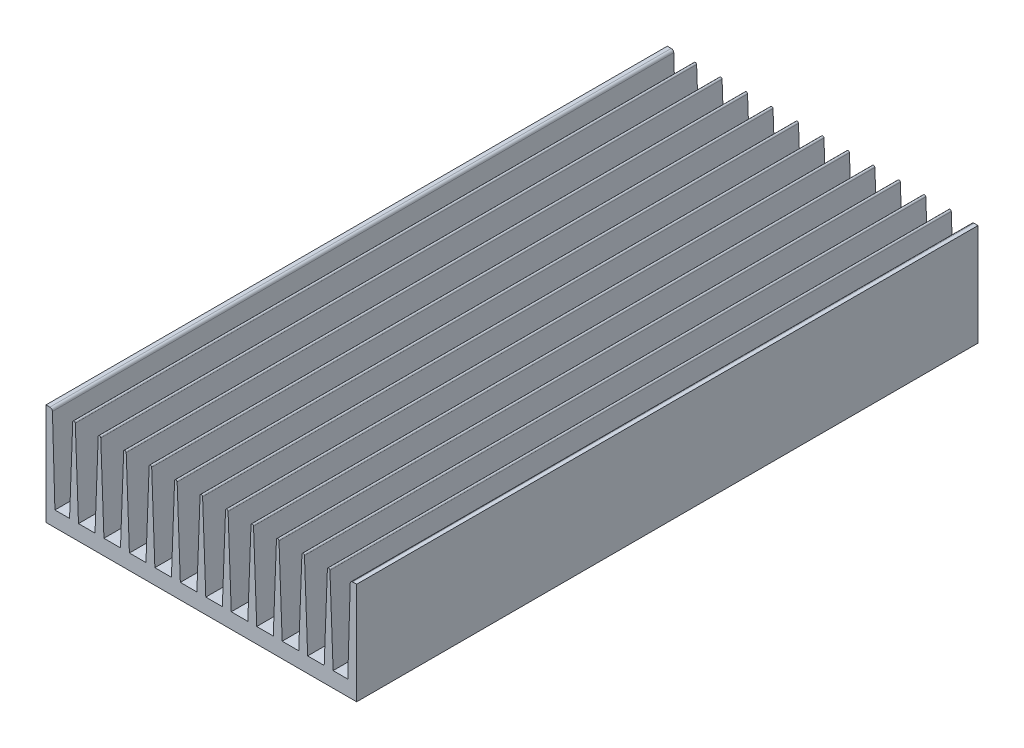
SolidWorks part; units mm, degrees
ref_plane "Спереди" through (0, 0, 0) normal (0, 0, 1) x (1, 0, 0)
ref_plane "Сверху" through (0, 0, 0) normal (0, 1, 0) x (1, 0, 0)
ref_plane "Справа" through (0, 0, 0) normal (1, 0, 0) x (0, 0, -1)
sketch "Эскиз1" plane through (0, 0, 0) normal (0, 0, 1) x (1, 0, 0)
  line L0 (0, 40) -> (1.529, 40)
  line L1 (0, 0) -> (122, 0)
  line L2 (2.5285, 39.0294) -> (3.5, 6)
  line L3 (0, 40) -> (0, 0)
  line L4 (122, 40) -> (122, 0)
  line L5 (61, 63.7127) -> (61, -22.2582) construction
  line L8 (122, 40) -> (120.471, 40)
  line L9 (119.4715, 39.0294) -> (118.5, 6)
  line L10 (3.5, 6) -> (118.5, 6)
  arc A0 (1.529, 40) -> (2.5285, 39.0294) centre (1.529, 39) cw
  arc A2 (120.471, 40) -> (119.4715, 39.0294) centre (120.471, 39) ccw
  point P18 (119.5, 40)
  dimension "D9" = 1
  dimension "D1" = 122
  dimension "D2" = 6
  dimension "D3" = 40
  dimension "D4" = 3.5
  dimension "D7" = 2.5
extrude "Вытянуть1" add sketch "Эскиз1" along normal blind 244
sketch "Эскиз2" plane through (0, 0, 244) normal (0, 0, 1) x (1, 0, 0)
  line L0 (118.5, 6) -> (3.5, 6) construction
  line L1 (10.5, 39.5) -> (9.25, 6)
  line L2 (11, 39.5) -> (11, 22.5548) construction
  line L3 (11.5, 39.5) -> (12.75, 6)
  line L4 (9.25, 6) -> (12.75, 6)
  line L6 (0, 40) -> (0, 0) construction
  arc A0 (10.5, 39.5) -> (11.5, 39.5) centre (11, 39.5) cw
  dimension "D1" = 34
  dimension "D3" = 0.5
  dimension "D2" = 3.5
  dimension "D4" = 11
  dimension "D5" = 1
extrude "Вытянуть3" add sketch "Эскиз2" against normal blind 244
pattern_curve "Кривая1" of "Вытянуть3" along edge at (61, 0, 0) parameters "D1"=11, "D3"=10, "D2"=1, "D4"=50
sketch "Эскиз3" plane through (0, 0, 0) normal (0, -1, 0) x (1, 0, 0)
  line L0 (-14.0506, 236) -> (137.5079, 236) construction
  line L1 (0, 244) -> (122, 244) construction
  line L2 (0, 244) -> (0, 0) construction
  line L3 (-46.7511, 122) -> (151.4312, 122) construction
  line L4 (0, 0) -> (122, 0) construction
  circle A0 centre (26, 236) radius 2.25
  circle A1 centre (96, 236) radius 2.25
  circle A2 centre (96, 8) radius 2.25
  circle A3 centre (26, 8) radius 2.25
  dimension "D2" = 70
  dimension "D4" = 4.5
  dimension "D1" = 8
  dimension "D3" = 26
extrude "Вырез-Вытянуть1" cut sketch "Эскиз3" against normal blind 6
sketch "Эскиз4" plane through (133.2401, 0, 310.1491) normal (0, -1, 0) x (-1, 0, 0)
  line L1 (133.2401, 66.1491) -> (133.2401, 310.1491) construction
  line L3 (133.2401, 310.1491) -> (11.2401, 310.1491) construction
  line L4 (83.2401, 178.1491) -> (103.8037, 178.1491) construction
  line L6 (61.2401, 178.1491) -> (61.2401, 283.1491) construction
  line L8 (69.2401, 144.1491) -> (69.2401, 163.1491) construction
  circle A2 centre (8.9901, 225.5491) radius 1.6
  circle A3 centre (83.2401, 178.1491) radius 1.15
  circle A4 centre (69.2401, 163.1491) radius 1.6
  circle A5 centre (61.2401, 283.1491) radius 1.6
  circle A6 centre (61.2401, 178.1491) radius 1.6
  circle A7 centre (107.2401, 178.1491) radius 1.15
  dimension "D3" = 3.2
  dimension "D5" = 132
  dimension "D6" = 2.3
  dimension "D7" = 3.2
  dimension "D2" = 147
  dimension "D12" = 24
  dimension "D13" = 64
  dimension "D14" = 132
  dimension "D15" = 72
extrude "Вырез-Вытянуть2" cut sketch "Эскиз4" against normal blind 6
cosmetic thread "Условное изображение резьбы12" parameters "D2"=4
cosmetic thread "Условное изображение резьбы13" parameters "D2"=4
cosmetic thread "Условное изображение резьбы14" parameters "D2"=3
cosmetic thread "Условное изображение резьбы16" parameters "D2"=4
cosmetic thread "Условное изображение резьбы17" parameters "D2"=3
